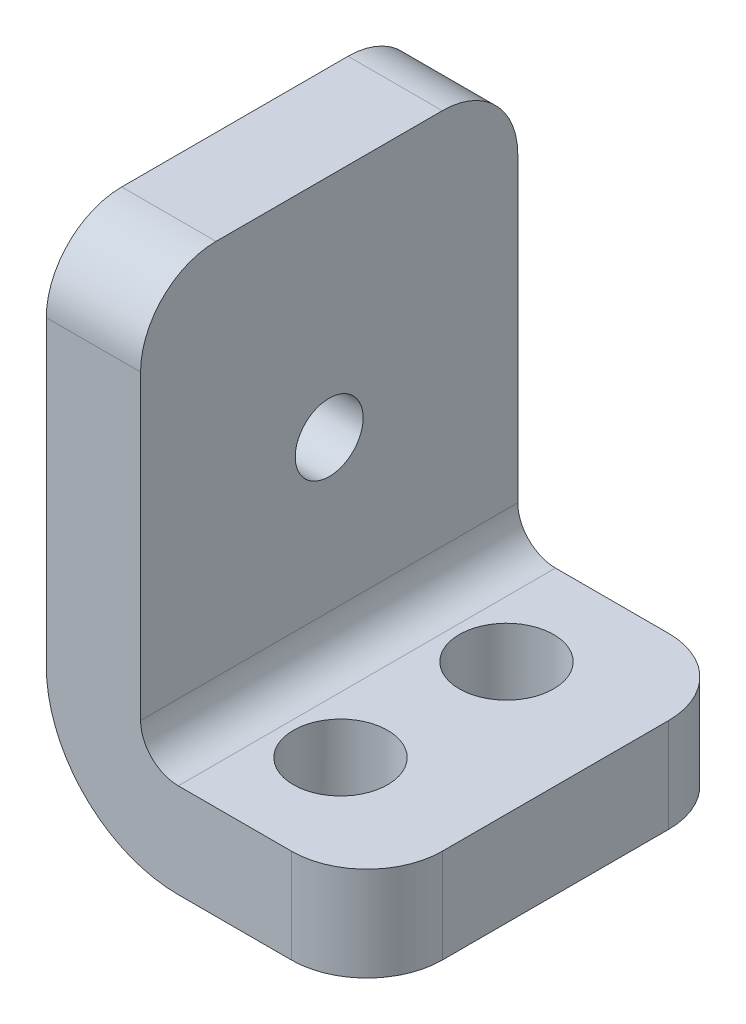
SolidWorks part; units mm, degrees
material "1060 Alloy"
ref_plane "Front Plane" through (0, 0, 0) normal (0, 0, 1) x (1, 0, 0)
ref_plane "Top Plane" through (0, 0, 0) normal (0, 1, 0) x (1, 0, 0)
ref_plane "Right Plane" through (0, 0, 0) normal (1, 0, 0) x (0, 0, -1)
sketch "Sketch1" plane through (0, 0, 0) normal (0, 0, 1) x (1, 0, 0)
  line L0 (0, 25.6908) -> (0, 12.9908)
  line L1 (1.27, 11.7208) -> (7.62, 11.7208)
  line L2 (-3.175, 25.6908) -> (-3.175, 12.9908)
  line L3 (1.27, 8.5458) -> (7.62, 8.5458)
  line L4 (-3.175, 25.6908) -> (0, 25.6908)
  line L5 (7.62, 11.7208) -> (7.62, 8.5458)
  arc A0 (1.27, 11.7208) -> (0, 12.9908) centre (1.27, 12.9908) cw
  arc A1 (1.27, 8.5458) -> (-3.175, 12.9908) centre (1.27, 12.9908) cw
  dimension "D1" = 1.27
  dimension "D2" = 6.35
  dimension "D3" = 12.7
  dimension "D4" = 3.175
extrude "Boss-Extrude1" add sketch "Sketch1" along normal blind 12.7
fillet "Fillet1" radius 2.54 4 edges at (7.62, 10.1333, 12.7) (7.62, 10.1333, 0) (-1.5875, 25.6908, 12.7) (-1.5875, 25.6908, 0)
sketch "Sketch2" plane through (0, 0, 0) normal (1, 0, 0) x (0, 0, -1)
  line L0 (-10.16, 25.6908) -> (-2.54, 25.6908) construction
  line L1 (0, 23.1508) -> (0, 12.9908) construction
  circle A0 centre (-6.35, 18.0708) radius 1.143
  point P6 (-6.35, 25.6908)
  point P10 (0, 18.0708)
  dimension "D1" = 2.286
extrude "Cut-Extrude1" cut sketch "Sketch2" against normal up to next from surface starting at face at (0, 20.7861, 6.35)
sketch "Sketch3" plane through (0, 11.7208, 0) normal (0, 1, 0) x (1, 0, 0)
  line L0 (3.175, -12.7) -> (3.175, 0)
  line L1 (5.08, -12.7) -> (1.27, -12.7) construction
  line L2 (5.08, 0) -> (1.27, 0) construction
  circle A0 centre (3.175, -9.144) radius 1.5875
  circle A1 centre (3.175, -3.556) radius 1.5875
  dimension "D1" = 3.556
  dimension "D3" = 3.175
  dimension "D4" = 3.175
  dimension "D2" = 3.556
extrude "Cut-Extrude2" cut sketch "Sketch3" against normal up to next contours L0 A0 | L0 A0 | L0 A1 | L0 A1 region at (2.5012, 11.7208, 9.144) region at (2.5012, 11.7208, 3.556) region at (3.8488, 11.7208, 3.556) region at (3.8488, 11.7208, 9.144)
sketch "Sketch4" plane through (0, 8.5458, 0) normal (0, -1, 0) x (1, 0, 0)
  line L0 (1.27, 6.35) -> (7.62, 6.35)
  line L1 (1.27, 12.7) -> (1.27, 0) construction
  line L2 (7.62, 10.16) -> (7.62, 2.54) construction
